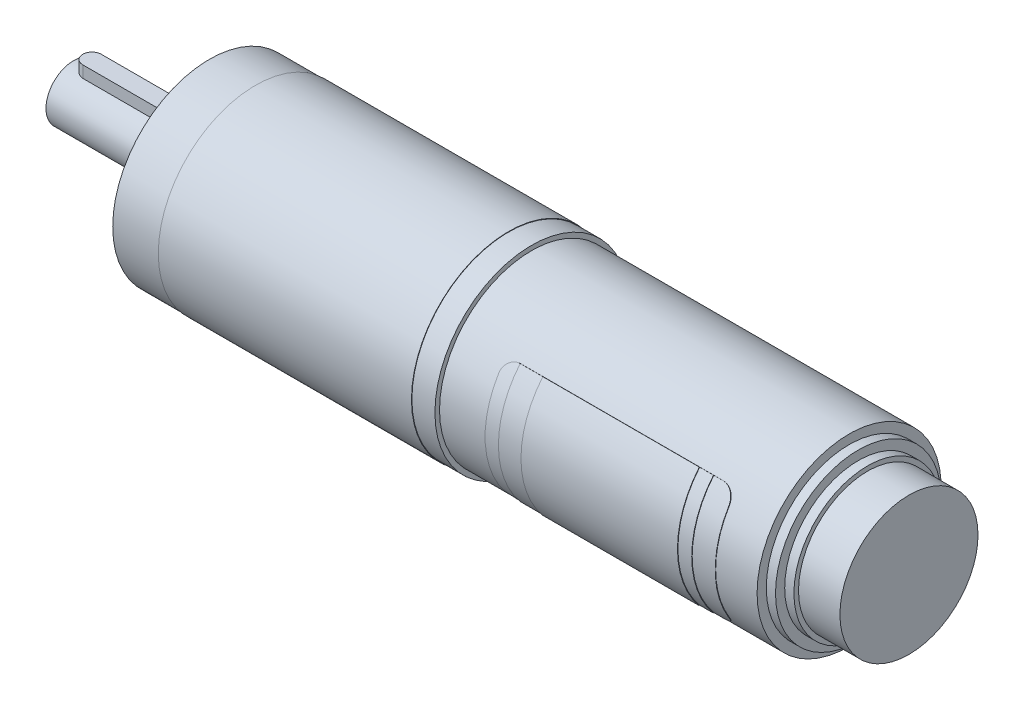
SolidWorks part; units mm, degrees
material "合金鋼 (SS)"
ref_plane "正面" through (0, 0, 0) normal (0, 0, 1) x (1, 0, 0)
ref_plane "平面" through (0, 0, 0) normal (0, 1, 0) x (1, 0, 0)
ref_plane "右側面" through (0, 0, 0) normal (1, 0, 0) x (0, 0, -1)
sketch "ｽｹｯﾁ1" plane through (0, 0, 0) normal (0, 0, 1) x (1, 0, 0)
  line L0 (-67.5005, 0) -> (135.9953, 0) construction
  line L1 (-99.5, 0) -> (-99.5, 6)
  line L2 (-99.5, 6) -> (-73, 6)
  line L3 (-73, 6) -> (-73, 14)
  line L4 (-73, 14) -> (-70, 14)
  line L5 (-70, 14) -> (-70, 21)
  line L6 (-70, 21) -> (-60, 21)
  line L7 (0, 21) -> (0, 20)
  line L8 (0, 20) -> (69, 20)
  line L9 (69, 20) -> (69, 18)
  line L10 (69, 18) -> (71, 18)
  line L11 (71, 18) -> (71, 16)
  line L12 (-99.5, 0) -> (73, 0)
  line L13 (71, 16) -> (73, 16)
  line L14 (73, 16) -> (73, 0)
  line L15 (82, 21.7038) -> (82, -16.0814) construction
  line L16 (-60, 21) -> (-60, 21.1)
  line L17 (-60, 21.1) -> (-5, 21.1)
  line L18 (-5, 21.1) -> (-5, 21)
  line L19 (-5, 21) -> (0, 21)
  dimension "D1" = 29.5
  dimension "D2" = 3
  dimension "D3" = 71
  dimension "D4" = 40
  dimension "D5" = 2
  dimension "D6" = 11
  dimension "D7" = 70
  dimension "D8" = 42
  dimension "D9" = 28
  dimension "D10" = 12
  dimension "D11" = 0.1
  dimension "D12" = 10
  dimension "D13" = 5
revolve "回転1" add sketch "ｽｹｯﾁ1" angle 360 about L0
sketch "ｽｹｯﾁ2" plane through (73, 0, 0) normal (1, 0, 0) x (0, 0, -1)
  line L0 (-15, 0) -> (-15, 26.2) construction
  line L1 (-15, 26.2) -> (15, 26.2) construction
  line L2 (15, 26.2) -> (15, 0) construction
  arc A0 (15, 0) -> (-15, 0) centre (0, 0) cw construction
  circle A1 centre (0, 0) radius 15
  dimension "D1" = 30
  dimension "D2" = 26.2
extrude "ﾎﾞｽ - 押し出し1" add sketch "ｽｹｯﾁ2" along normal up to vertex (9 mm away) from vertex up to point (82, 21.7038, 0) starting at point (73, 26.2, 15)
sketch "ｽｹｯﾁ3" plane through (0, 0, 0) normal (0, 1, 0) x (1, 0, 0)
  line L0 (-82, 0) -> (-73.4713, 0) construction
  line L2 (-95.5, 0) -> (-79.5, 0) construction
  line L3 (-95.5, 2) -> (-79.5, 2)
  line L4 (-95.5, -2) -> (-79.5, -2)
  line L5 (-99.5, 6) -> (-99.5, -6) construction
  arc A0 (-95.5, 2) -> (-95.5, -2) centre (-95.5, 0) ccw
  arc A1 (-79.5, -2) -> (-79.5, 2) centre (-79.5, 0) ccw
  point P3 (-87.5, 0)
  point P10 (-97.5, 0)
  point P11 (-77.5, 0)
  dimension "D1" = 20
  dimension "D2" = 4
  dimension "D3" = 2
extrude "ｶｯﾄ - 押し出し1" cut sketch "ｽｹｯﾁ3" against normal blind 1.8 from vertex starting at point (-99.5, 6, 0)
extrude "ﾎﾞｽ - 押し出し3" add sketch "ｽｹｯﾁ3<2>" along normal blind 2.2 and the other way blind 1.8 from vertex separate body starting at point (-99.5, 6, 0)
sketch "ｽｹｯﾁ3<2>" plane through (0, 0, 0) normal (0, 1, 0) x (1, 0, 0) same geometry as "ｽｹｯﾁ3"
sketch "ｽｹｯﾁ7" plane through (0, 0, 0) normal (0, 1, 0) x (1, 0, 0)
  line L0 (0, 0) -> (50000, 0) construction
  line L1 (10, -20) -> (10, -20.1)
  line L2 (0, -20) -> (69, -20) construction
  line L3 (10, -20.1) -> (13, -20.1)
  line L4 (13, -20.1) -> (13, -20.2)
  line L5 (13, -20.2) -> (18, -20.2)
  line L6 (18, -20.2) -> (18, -20.3)
  line L7 (18, -20.3) -> (52, -20.3)
  line L8 (52, -20.3) -> (52, -20.2)
  line L9 (52, -20.2) -> (55, -20.2)
  line L10 (55, -20.2) -> (55, -20.1)
  line L11 (55, -20.1) -> (60, -20.1)
  line L12 (60, -20.1) -> (60, -20)
  line L13 (10, -20) -> (60, -20)
  dimension "D1" = 50
  dimension "D2" = 3
  dimension "D3" = 5
  dimension "D4" = 3
  dimension "D5" = 5
  dimension "D6" = 0.1
  dimension "D7" = 0.1
  dimension "D8" = 0.1
  dimension "D9" = 10
revolve "回転2" add sketch "ｽｹｯﾁ7" angle 40 about L0 other way angle 40
fillet "ﾌｨﾚｯﾄ1" radius 3 4 edges at (10, 12.8879, 15.3592) (10, -12.8879, 15.3592) (60, 12.8879, 15.3592) (60, -12.8879, 15.3592)
hole_wizard "Ø4.0 (4) 直径の穴1" positions "ｽｹｯﾁ10" profile "ｽｹｯﾁ9" hole size "Ø4.0" standard "Jis"
sketch "ｽｹｯﾁ10" plane through (-70, 0, 0) normal (-1, 0, 0) x (0, 0, 1)
  circle A3 centre (0, 0) radius 17.5 construction
  point P28 (0, 17.5)
  point P30 (-17.5, 0)
  point P32 (0, -17.5)
  point P34 (17.5, 0)
  dimension "D1" = 35
sketch "ｽｹｯﾁ9" plane through (-70, 17.5, 0) normal (0, 1, 0) x (0, 0, 1)
  line L0 (0, 0) -> (0, 7.2017)
  line L1 (0, 7.2017) -> (2, 6)
  line L2 (2, 6) -> (2, 0)
  line L5 (2, 0) -> (0, 0)
  line L10 (0, 7.2017) -> (-2, 6) construction
  line L11 (0, -6.35) -> (0, 107.95) construction
  dimension "穴の直径" = 4
  dimension "穴の深さ" = 6
  dimension "ﾄﾞﾘﾙ角度" = 118
